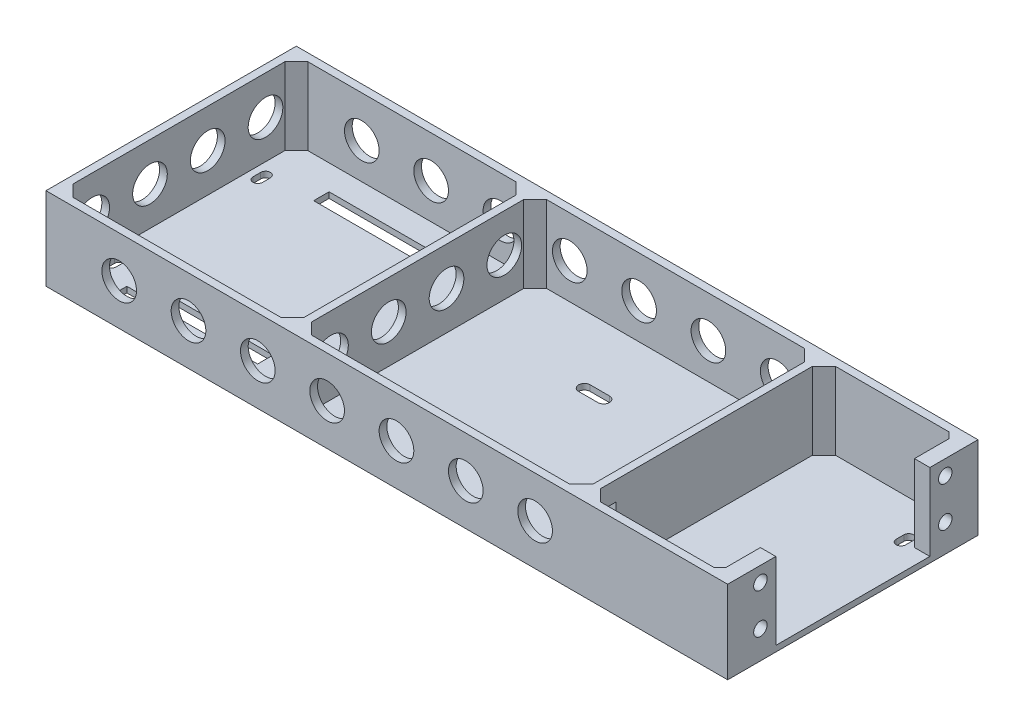
SolidWorks part; units mm, degrees
ref_plane "Спереди" through (0, 0, 0) normal (0, 0, 1) x (1, 0, 0)
ref_plane "Сверху" through (0, 0, 0) normal (0, 1, 0) x (1, 0, 0)
ref_plane "Справа" through (0, 0, 0) normal (1, 0, 0) x (0, 0, -1)
sketch "Эскиз1" plane through (0, 0, 0) normal (0, 1, 0) x (1, 0, 0)
  line L1 (-87.5, -32.5) -> (87.5, -32.5)
  line L2 (-87.5, -32.5) -> (-87.5, 32.5)
  line L3 (-87.5, 32.5) -> (87.5, 32.5)
  line L4 (87.5, -32.5) -> (87.5, 32.5)
  line L5 (-87.5, -32.5) -> (87.5, 32.5) construction
  line L6 (-87.5, 32.5) -> (87.5, -32.5) construction
  point P0 (0, 0)
  dimension "D1" = 175
  dimension "D2" = 65
extrude "Бобышка-Вытянуть1" add sketch "Эскиз1" along normal blind 1.5
sketch "Эскиз3" plane through (0, 1.5, 0) normal (0, 1, 0) x (1, 0, 0)
  line L5 (-87.5, -32.5) -> (87.5, -32.5)
  line L6 (-87.5, -32.5) -> (-87.5, 32.5)
  line L7 (-87.5, 32.5) -> (87.5, 32.5)
  line L8 (85.5, -30.5) -> (85.5, 30.5)
  line L9 (85.5, 30.5) -> (-85.5, 30.5)
  line L10 (-85.5, 30.5) -> (-85.5, -30.5)
  line L11 (-85.5, -30.5) -> (85.5, -30.5)
  line L12 (85.5, -30.5) -> (85.5, 30.5)
  line L13 (85.5, 30.5) -> (-85.5, 30.5)
  line L14 (-85.5, 30.5) -> (-85.5, -30.5)
  line L15 (-85.5, -30.5) -> (85.5, -30.5)
  line L16 (87.5, -32.5) -> (87.5, 32.5)
  line L17 (-87.5, -32.5) -> (87.5, 32.5) construction
  line L18 (-87.5, 32.5) -> (87.5, -32.5) construction
  point P0 (0, 0)
  dimension "D1" = 2
extrude "Бобышка-Вытянуть2" add sketch "Эскиз3" along normal blind 20
sketch "Эскиз4" plane through (87.5, 0, 0) normal (1, 0, 0) x (0, 0, -1)
  line L7 (-32.5, 21.5) -> (32.5, 21.5) construction
  line L8 (-20, 21.5) -> (20, 21.5)
  line L9 (-20, 21.5) -> (-20, 1.5)
  line L10 (-20, 1.5) -> (20, 1.5)
  line L11 (20, 21.5) -> (20, 1.5)
  line L12 (-32.5, 21.5) -> (-32.5, 0) construction
  dimension "D1" = 40
  dimension "D2" = 20
  dimension "D3" = 12.5
extrude "Вырез-Вытянуть1" cut sketch "Эскиз4" against normal blind 2
sketch "Эскиз5" plane through (0, 1.5, 0) normal (0, 1, 0) x (1, 0, 0)
  line L0 (57.5, 20) -> (57.5, 30.5)
  line L1 (87.5, 20) -> (57.5, 20)
  line L2 (87.5, 20) -> (87.5, -20)
  line L3 (87.5, -20) -> (57.5, -20)
  line L4 (57.5, 20) -> (57.5, -20)
  line L5 (85.5, 30.5) -> (-85.5, 30.5) construction
  line L6 (57.5, -20) -> (57.5, -30.5)
  line L7 (-85.5, -30.5) -> (85.5, -30.5) construction
  dimension "D1" = 30
  dimension "D2" = 40
sketch "Эскиз6" plane through (87.5, 0, 0) normal (1, 0, 0) x (0, 0, -1)
  line L0 (-32.5, 21.5) -> (-20, 21.5) construction
  line L1 (-20, 21.5) -> (-20, 1.5) construction
  circle A1 centre (-24, 7.25) radius 1.75
  circle A5 centre (-24, 17.65) radius 1.75
  dimension "D1" = 3.5
  dimension "D3" = 3.5
  dimension "D5" = 3.85
  dimension "D2" = 4
  dimension "D4" = 14.25
  dimension "D6" = 4
extrude "Вырез-Вытянуть2" cut sketch "Эскиз6" against normal blind 2
ref_plane "Плоскость2" through (0, 0, 0) normal (0, 0, -1) x (-1, 0, 0)
mirror "Зеркальное отражение2" about plane through (0, 0, 0) normal (0, 0, -1) of "Вырез-Вытянуть2"
sketch "Эскиз9" plane through (0, 1.5, 0) normal (0, 1, 0) x (1, 0, 0)
  line L0 (85.5, 20) -> (85.5, 30.5) construction
  line L1 (49.5, 30.5) -> (51.5, 30.5)
  line L2 (49.5, 30.5) -> (49.5, -30.5)
  line L3 (49.5, -30.5) -> (51.5, -30.5)
  line L4 (51.5, 30.5) -> (51.5, -30.5)
  line L5 (85.5, 30.5) -> (-85.5, 30.5) construction
  line L6 (-85.5, -30.5) -> (85.5, -30.5) construction
  dimension "D1" = 2
  dimension "D2" = 34
  dimension "D3" = 0
  dimension "D4" = 0
extrude "Бобышка-Вытянуть4" add sketch "Эскиз9" along normal blind 20
sketch "Эскиз12" plane through (51.5, 0, 0) normal (1, 0, 0) x (0, 0, -1)
  line L0 (-30.5, 21.5) -> (30.5, 21.5) construction
  line L1 (-27.5, 16.5) -> (-23.5, 16.5)
  line L2 (-27.5, 16.5) -> (-27.5, 6.5)
  line L3 (-27.5, 6.5) -> (-23.5, 6.5)
  line L4 (-23.5, 16.5) -> (-23.5, 6.5)
  line L5 (-30.5, 21.5) -> (-30.5, 1.5) construction
  dimension "D1" = 10
  dimension "D2" = 4
  dimension "D3" = 5
  dimension "D4" = 3
extrude "Вырез-Вытянуть4" cut sketch "Эскиз12" against normal blind 2
chamfer "Фаска1" distance 3 angle 45 4 edges at (-85.5, 11.5, -30.5) (49.5, 11.5, 30.5) (49.5, 11.5, -30.5) (-85.5, 11.5, 30.5)
chamfer "Фаска2" distance 3 angle 45 2 edges at (51.5, 11.5, -30.5) (51.5, 11.5, 30.5)
chamfer "Фаска3" distance 1.5 angle 45 2 edges at (85.5, 11.5, 30.5) (85.5, 11.5, -30.5)
sketch "Эскиз13" plane through (0, 0, -32.5) normal (0, 0, -1) x (-1, 0, 0)
  line L21 (-87.5, 10.75) -> (86.3564, 10.75) construction
  line L22 (-87.5, 21.5) -> (-87.5, 0) construction
  line L23 (-49.5, 16.5) -> (-49.5, 21.5) construction
  circle A0 centre (-39.5, 10.75) radius 4.5
  dimension "D2" = 9
  dimension "D1" = 10
extrude "Вырез-Вытянуть5" cut sketch "Эскиз13" against normal blind 71
ref_plane "Плоскость3" through (39.5, 0, 0) normal (-1, 0, 0) x (0, 0, 1)
pattern_linear "Линейный массив1" count 7 spacing 18 along (-1, 0, 0) of "Вырез-Вытянуть5"
sketch "Эскиз14" plane through (0, 1.5, 0) normal (0, 1, 0) x (1, 0, 0)
  line L0 (-85.5, 27.5) -> (-85.5, -27.5) construction
  line L1 (-25.5, 30.5) -> (-23.5, 30.5)
  line L2 (-25.5, 30.5) -> (-25.5, -30.5)
  line L3 (-25.5, -30.5) -> (-23.5, -30.5)
  line L4 (-23.5, 30.5) -> (-23.5, -30.5)
  line L5 (46.5, 30.5) -> (-82.5, 30.5) construction
  line L6 (-82.5, -30.5) -> (46.5, -30.5) construction
  point P6 (-24.5, 30.5)
  dimension "D1" = 60
  dimension "D2" = 0
  dimension "D3" = 0
  dimension "D4" = 2
extrude "Бобышка-Вытянуть5" add sketch "Эскиз14" along normal blind 20
chamfer "Фаска4" distance 3 angle 45 2 edges at (-25.5, 11.5, 30.5) (-25.5, 11.5, -30.5)
chamfer "Фаска5" distance 3 angle 45 2 edges at (-23.5, 11.5, 30.5) (-23.5, 11.5, -30.5)
sketch "Эскиз15" plane through (-23.5, 0, 0) normal (1, 0, 0) x (0, 0, -1)
  line L20 (-27.5, 11.5) -> (27.5, 11.5) construction
  line L33 (-27.5, 21.5) -> (-27.5, 1.5) construction
  line L34 (27.5, 1.5) -> (27.5, 21.5) construction
  circle A0 centre (-22.5, 11.5) radius 4.5
  dimension "D1" = 9
  dimension "D2" = 5
extrude "Вырез-Вытянуть6" cut sketch "Эскиз15" against normal blind 71
pattern_linear "Линейный массив2" count 4 spacing 15 along (0, 0, -1) of "Вырез-Вытянуть6"
sketch "Эскиз16" plane through (0, 1.5, 0) normal (0, 1, 0) x (1, 0, 0)
  line L3 (6.8, 13) -> (11.8, 13) construction
  line L4 (6.8, 14.5) -> (11.8, 14.5)
  line L5 (6.8, 11.5) -> (11.8, 11.5)
  line L7 (46.5, 30.5) -> (-20.5, 30.5) construction
  line L8 (39.5, 13) -> (44.5, 13) construction
  line L9 (39.5, 14.5) -> (44.5, 14.5)
  line L10 (39.5, 11.5) -> (44.5, 11.5)
  line L11 (49.5, 27.5) -> (49.5, -27.5) construction
  arc A2 (6.8, 14.5) -> (6.8, 11.5) centre (6.8, 13) ccw
  arc A3 (11.8, 11.5) -> (11.8, 14.5) centre (11.8, 13) ccw
  arc A4 (39.5, 14.5) -> (39.5, 11.5) centre (39.5, 13) ccw
  arc A5 (44.5, 11.5) -> (44.5, 14.5) centre (44.5, 13) ccw
  point P2 (9.3, 13)
  point P11 (42, 13)
  dimension "D1" = 5
  dimension "D2" = 3
  dimension "D3" = 16
  dimension "D4" = 16
  dimension "D5" = 5
  dimension "D6" = 5
  dimension "D7" = 32.7
extrude "Вырез-Вытянуть7" cut sketch "Эскиз16" against normal blind 4
sketch "Эскиз17" plane through (0, 1.5, 0) normal (0, 1, 0) x (1, 0, 0)
  line L1 (-21.4057, 21.2837) -> (3.5943, 21.2837)
  line L2 (-21.4057, 21.2837) -> (-21.4057, -18.7163)
  line L3 (-21.4057, -18.7163) -> (3.5943, -18.7163)
  line L4 (3.5943, 21.2837) -> (3.5943, -18.7163)
  dimension "D1" = 25
  dimension "D2" = 40
sketch "Эскиз18" plane through (0, 1.5, 0) normal (0, 1, 0) x (1, 0, 0)
  line L1 (-70.5, 24) -> (-43.5, 24)
  line L2 (-70.5, 24) -> (-70.5, 20)
  line L3 (-70.5, 20) -> (-43.5, 20)
  line L4 (-43.5, 24) -> (-43.5, 20)
  line L5 (-68.0533, -20) -> (-41.0533, -20)
  line L6 (-68.0533, -20) -> (-68.0533, -24)
  line L7 (-68.0533, -24) -> (-41.0533, -24)
  line L8 (-41.0533, -20) -> (-41.0533, -24)
  line L9 (-28.5, 30.5) -> (-82.5, 30.5) construction
  line L12 (-85.5, 27.5) -> (-85.5, -27.5) construction
  dimension "D1" = 40
  dimension "D2" = 6.5
  dimension "D3" = 4
  dimension "D4" = 4
  dimension "D5" = 15
  dimension "D6" = 27
extrude "Вырез-Вытянуть8" cut sketch "Эскиз18" against normal blind 5
sketch "Эскиз19" plane through (0, 1.5, 0) normal (0, 1, 0) x (1, 0, 0)
  line L0 (82.5, 21.5) -> (82.5, 19.5) construction
  line L1 (83.75, 21.5) -> (83.75, 19.5)
  line L2 (81.25, 21.5) -> (81.25, 19.5)
  line L3 (82.5, -18.5) -> (82.5, -20.5) construction
  line L4 (83.75, -18.5) -> (83.75, -20.5)
  line L5 (81.25, -18.5) -> (81.25, -20.5)
  line L6 (82.5, 30.5) -> (82.5, -30.5) construction
  line L7 (84, 30.5) -> (54.5, 30.5) construction
  line L8 (54.5, -30.5) -> (84, -30.5) construction
  line L9 (85.5, 20) -> (85.5, 29) construction
  line L10 (-82.5, 30.5) -> (-82.5, -30.5) construction
  line L11 (-28.5, 30.5) -> (-82.5, 30.5) construction
  line L12 (-82.5, -30.5) -> (-28.5, -30.5) construction
  line L13 (-85.5, 27.5) -> (-85.5, -27.5) construction
  line L15 (-82.5, 19.5) -> (-82.5, 17.5) construction
  line L16 (-81.25, 19.5) -> (-81.25, 17.5)
  line L17 (-83.75, 19.5) -> (-83.75, 17.5)
  line L18 (-82.5, -18.5) -> (-82.5, -20.5) construction
  line L19 (-81.25, -18.5) -> (-81.25, -20.5)
  line L20 (-83.75, -18.5) -> (-83.75, -20.5)
  arc A0 (83.75, 21.5) -> (81.25, 21.5) centre (82.5, 21.5) ccw
  arc A1 (81.25, 19.5) -> (83.75, 19.5) centre (82.5, 19.5) ccw
  arc A2 (83.75, -18.5) -> (81.25, -18.5) centre (82.5, -18.5) ccw
  arc A3 (81.25, -20.5) -> (83.75, -20.5) centre (82.5, -20.5) ccw
  arc A4 (-81.25, 19.5) -> (-83.75, 19.5) centre (-82.5, 19.5) ccw
  arc A5 (-83.75, 17.5) -> (-81.25, 17.5) centre (-82.5, 17.5) ccw
  arc A6 (-81.25, -18.5) -> (-83.75, -18.5) centre (-82.5, -18.5) ccw
  arc A7 (-83.75, -20.5) -> (-81.25, -20.5) centre (-82.5, -20.5) ccw
  point P2 (82.5, 20.5)
  point P9 (82.5, -19.5)
  point P35 (-82.5, 18.5)
  point P42 (-82.5, -19.5)
  dimension "D1" = 2
  dimension "D2" = 2.5
  dimension "D3" = 40
  dimension "D4" = 10
  dimension "D5" = 3
  dimension "D6" = 3
  dimension "D7" = 2.5
  dimension "D8" = 2
  dimension "D9" = 2
  dimension "D10" = 2.5
  dimension "D11" = 40
  dimension "D12" = 10
extrude "Вырез-Вытянуть9" cut sketch "Эскиз19" against normal blind 10
sketch "Эскиз21" plane through (0, 1.5, 0) normal (0, 1, 0) x (1, 0, 0)
  line L0 (85.5, -29) -> (85.5, -20) construction
  line L1 (75.5, -23.5) -> (69.5, -23.5)
  line L2 (75.5, -23.5) -> (75.5, -29.5)
  line L3 (75.5, -29.5) -> (69.5, -29.5)
  line L4 (69.5, -23.5) -> (69.5, -29.5)
  line L5 (54.5, -30.5) -> (84, -30.5) construction
  dimension "D1" = 6
  dimension "D2" = 6
  dimension "D3" = 10
  dimension "D4" = 1
extrude "Вырез-Вытянуть10" cut sketch "Эскиз21" against normal blind 10
pattern_linear "Линейный массив3" count 2 spacing 145 along (-1, 0, 0) of "Вырез-Вытянуть10"
sketch "Эскиз24" plane through (87.5, 0, 0) normal (1, 0, 0) x (0, 0, -1)
  line L0 (-32.5, 21.5) -> (-20, 21.5)
  line L1 (-20, 21.5) -> (-20, 1.5)
  line L2 (-20, 1.5) -> (20, 1.5)
  line L3 (20, 1.5) -> (20, 21.5)
  line L4 (20, 21.5) -> (32.5, 21.5)
  line L5 (32.5, 21.5) -> (32.5, 0)
  line L6 (32.5, 0) -> (-32.5, 0)
  line L7 (-32.5, 0) -> (-32.5, 21.5)
  circle A0 centre (-24, 17.65) radius 1.75
  circle A1 centre (-24, 7.25) radius 1.75
  circle A2 centre (24, 17.65) radius 1.75
  circle A3 centre (24, 7.25) radius 1.75
extrude "Бобышка-Вытянуть6" add sketch "Эскиз24" along normal blind 2
